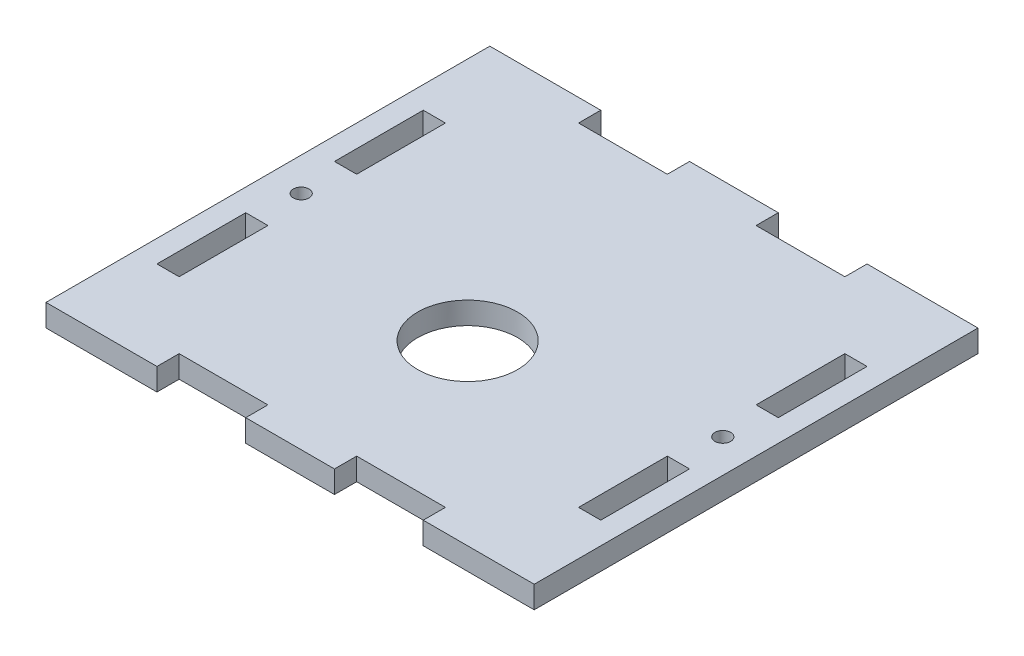
SolidWorks part; units mm, degrees
ref_plane "Front Plane" through (0, 0, 0) normal (0, 0, 1) x (1, 0, 0)
ref_plane "Top Plane" through (0, 0, 0) normal (0, 1, 0) x (1, 0, 0)
ref_plane "Right Plane" through (0, 0, 0) normal (1, 0, 0) x (0, 0, -1)
sketch "Sketch1" plane through (0, 0, 0) normal (0, 1, 0) x (1, 0, 0)
  line L1 (0, 0) -> (139.7, 0)
  line L2 (0, 0) -> (0, 127)
  line L3 (0, 127) -> (139.7, 127)
  line L4 (139.7, 0) -> (139.7, 127)
  dimension "D1" = 127
  dimension "D2" = 139.7
extrude "Boss-Extrude1" add sketch "Sketch1" along normal blind 6.35
sketch "Sketch13" plane through (0, 6.35, 0) normal (0, 1, 0) x (1, 0, 0)
  line L0 (0, 0) -> (139.7, 0) construction
  line L1 (31.75, 0) -> (57.15, 0)
  line L2 (31.75, 0) -> (31.75, 6.35)
  line L3 (31.75, 6.35) -> (57.15, 6.35)
  line L4 (57.15, 0) -> (57.15, 6.35)
  line L5 (82.55, 6.35) -> (107.95, 6.35)
  line L6 (107.95, 0) -> (107.95, 6.35)
  line L7 (82.55, 0) -> (107.95, 0)
  line L8 (82.55, 0) -> (82.55, 6.35)
  line L17 (31.75, 6.35) -> (82.55, 6.35) construction
  line L18 (0, 127) -> (0, 0) construction
  dimension "D1" = 25.4
  dimension "D2" = 6.35
  dimension "D4" = 50.8
  dimension "D5" = 31.75
  dimension "D3" = 2
extrude "Cut-Extrude6" cut sketch "Sketch13" against normal blind 6.35
pattern_linear "LPattern7" count 2 spacing 120.65 along (0, 0, -1) of "Cut-Extrude6"
sketch "Sketch14" plane through (0, 6.35, 0) normal (0, 1, 0) x (1, 0, 0)
  line L0 (0, 127) -> (0, 0) construction
  line L1 (6.35, 25.4) -> (12.7, 25.4)
  line L2 (6.35, 25.4) -> (6.35, 50.8)
  line L3 (6.35, 50.8) -> (12.7, 50.8)
  line L4 (12.7, 25.4) -> (12.7, 50.8)
  line L5 (0, 0) -> (31.75, 0) construction
  line L6 (127, 50.8) -> (133.35, 50.8)
  line L7 (127, 25.4) -> (127, 50.8)
  line L8 (133.35, 25.4) -> (133.35, 50.8)
  line L9 (127, 25.4) -> (133.35, 25.4)
  line L10 (127, 101.6) -> (133.35, 101.6)
  line L11 (127, 76.2) -> (127, 101.6)
  line L12 (133.35, 76.2) -> (133.35, 101.6)
  line L13 (127, 76.2) -> (133.35, 76.2)
  line L14 (6.35, 101.6) -> (12.7, 101.6)
  line L15 (6.35, 76.2) -> (6.35, 101.6)
  line L16 (12.7, 76.2) -> (12.7, 101.6)
  line L17 (6.35, 76.2) -> (12.7, 76.2)
  dimension "D1" = 25.4
  dimension "D2" = 6.35
  dimension "D3" = 6.35
  dimension "D4" = 25.4
  dimension "D5" = 2
  dimension "D6" = 2
extrude "Cut-Extrude7" cut sketch "Sketch14" against normal blind 6.35
hole_wizard "#8 Clearance Hole1" positions "Sketch16" profile "Sketch15" hole size "#8" standard "ANSI Inch"
sketch "Sketch16" plane through (0, 6.35, 0) normal (0, 1, 0) x (1, 0, 0)
  line L0 (12.7, 50.8) -> (6.35, 50.8) construction
  line L1 (6.35, 50.8) -> (6.35, 25.4) construction
  line L2 (133.35, 50.8) -> (127, 50.8) construction
  line L3 (127, 50.8) -> (127, 25.4) construction
  point P0 (9.525, 63.5)
  point P3 (9.525, 50.8)
  point P8 (130.175, 63.5)
  dimension "D1" = 12.7
  dimension "D2" = 3.175
  dimension "D3" = 12.7
  dimension "D4" = 3.175
sketch "Sketch15" plane through (9.525, 6.35, -63.5) normal (1, 0, 0) x (0, 0, 1)
  line L0 (0, 0) -> (0, 11.5107)
  line L1 (0, 11.5107) -> (2.2479, 10.16)
  line L2 (2.2479, 10.16) -> (2.2479, 0)
  line L5 (2.2479, 0) -> (0, 0)
  line L10 (0, 11.5107) -> (-2.2479, 10.16) construction
  line L11 (0, -6.35) -> (0, 107.95) construction
  dimension "Hole Dia." = 4.4958
  dimension "Hole Depth" = 10.16
  dimension "Drill Angle" = 118
sketch "Sketch18" plane through (0, 6.35, 0) normal (0, 1, 0) x (1, 0, 0)
  line L0 (0, 127) -> (0, 0) construction
  line L1 (107.95, 6.35) -> (82.55, 6.35) construction
  circle A0 centre (69.85, 50.8) radius 14.2875
  dimension "D1" = 28.575
  dimension "D2" = 69.85
  dimension "D3" = 44.45
extrude "Cut-Extrude9" cut sketch "Sketch18" against normal blind 7.62
equation "\"THICK\"= .25"
